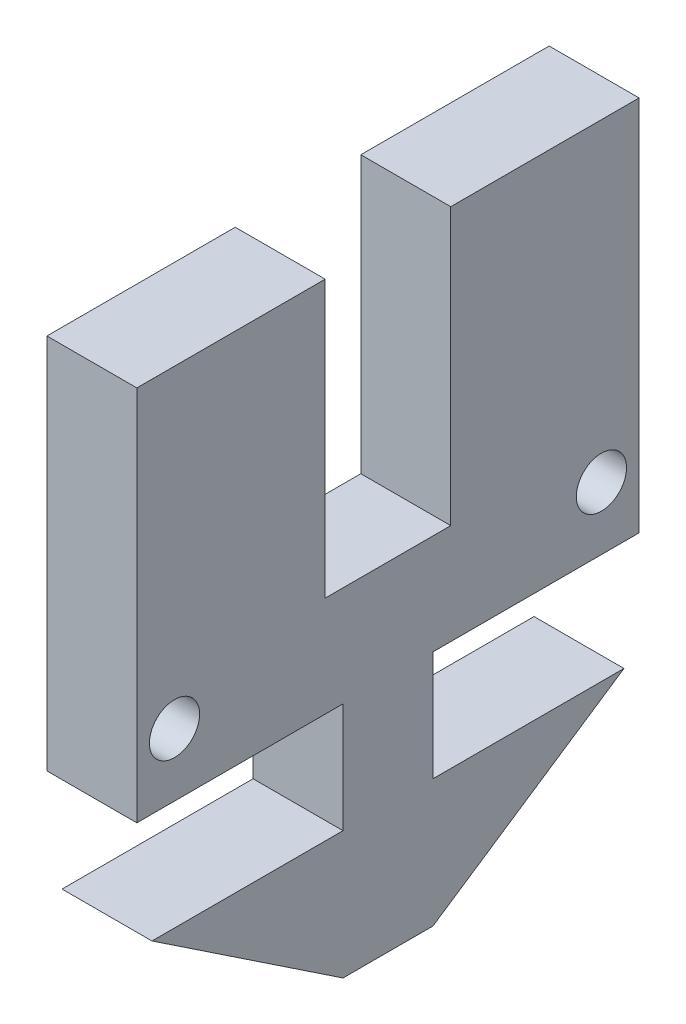
SolidWorks part; units mm, degrees
ref_plane "Front Plane" through (0, 0, 0) normal (0, 0, 1) x (1, 0, 0)
ref_plane "Top Plane" through (0, 0, 0) normal (0, 1, 0) x (1, 0, 0)
ref_plane "Right Plane" through (0, 0, 0) normal (1, 0, 0) x (0, 0, -1)
sketch "Sketch1" plane through (0, 0, 0) normal (1, 0, 0) x (0, 0, -1)
  line L0 (-2.5, 7.5) -> (-2.5, -3.5)
  line L1 (-10, -7.5) -> (10, -7.5)
  line L2 (-10, -7.5) -> (-10, 7.5)
  line L3 (-10, 7.5) -> (-2.5, 7.5)
  line L4 (10, -7.5) -> (10, 7.5)
  line L5 (-10, -7.5) -> (10, 7.5) construction
  line L6 (-10, 7.5) -> (10, -7.5) construction
  line L7 (-2.5, -3.5) -> (2.5, -3.5)
  line L8 (2.5, -3.5) -> (2.5, 7.5)
  line L9 (2.5, 7.5) -> (10, 7.5)
  point P0 (0, 0)
  point P8 (0, -3.5)
  dimension "D1" = 15
  dimension "D2" = 20
  dimension "D3" = 5
  dimension "D4" = 11
extrude "Boss-Extrude1" add sketch "Sketch1" along normal blind 3.5814
sketch "Sketch7" plane through (3.5814, 0, 0) normal (1, 0, 0) x (0, 0, -1)
  line L0 (-10, 7.5) -> (-10, -7.5) construction
  line L1 (-2.5, -3.5) -> (2.5, -3.5) construction
  circle A0 centre (-8.5, -5) radius 1
  dimension "D1" = 2
  dimension "D2" = 1.5
  dimension "D3" = 1.5
extrude "Cut-Extrude5" cut sketch "Sketch7" against normal through all
mirror "Mirror2" about plane through (0, 0, 0) normal (0, 0, 1) of "Cut-Extrude5"
sketch "Sketch8" plane through (0, 0, 0) normal (1, 0, 0) x (0, 0, -1)
  line L9 (-1.7907, -11.875) -> (-9.398, -11.875)
  line L10 (-1.7907, -7.5) -> (-1.7907, -11.875)
  line L11 (1.7907, -7.5) -> (1.7907, -11.875)
  line L12 (-9.398, -11.875) -> (-1.7907, -16.955)
  line L13 (-1.7907, -16.955) -> (1.7907, -16.955)
  line L14 (1.7907, -16.955) -> (9.398, -11.875)
  line L15 (9.398, -11.875) -> (1.7907, -11.875)
  line L16 (-10, -7.5) -> (10, -7.5) construction
  line L17 (-1.7907, -7.5) -> (1.7907, -7.5)
  point P0 (0, -9.6875)
  point P9 (0, -16.955)
  point P10 (1.7907, -9.6875)
  dimension "D1" = 3.5814
  dimension "D2" = 4.375
  dimension "D3" = 18.796
  dimension "D4" = 5.08
extrude "Boss-Extrude3" add sketch "Sketch8" along normal up to surface (3.5814 mm away) up to face at (3.5814, -5, -7.5)
